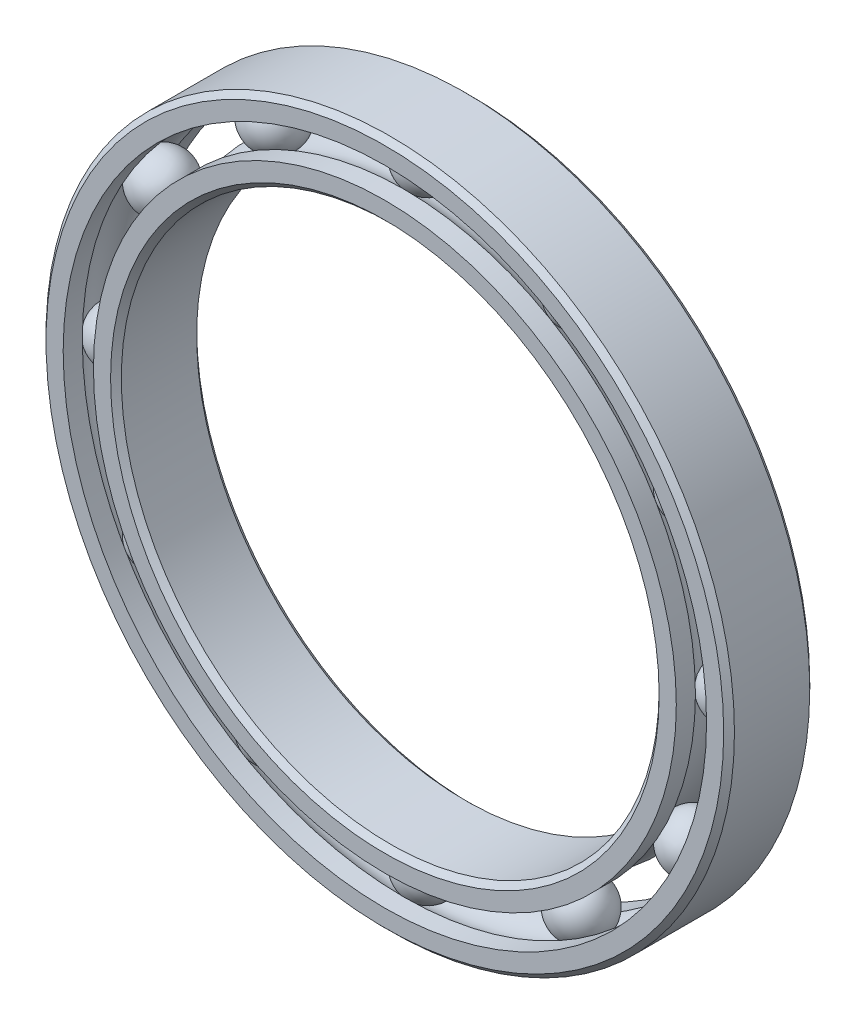
SolidWorks part; units mm, degrees
ref_plane "Front Plane" through (0, 0, 0) normal (0, 0, 1) x (1, 0, 0)
ref_plane "Top Plane" through (0, 0, 0) normal (0, 1, 0) x (1, 0, 0)
ref_plane "Right Plane" through (0, 0, 0) normal (1, 0, 0) x (0, 0, -1)
sketch "Sketch1" plane through (0, 0, 0) normal (1, 0, 0) x (0, 0, -1)
  line L0 (-2, 0) -> (2, 0) construction
  line L1 (0, 16) -> (0, -16) construction
  line L2 (1.75, 16) -> (-1.75, 16)
  line L3 (-1.75, 16) -> (-2, 15.75)
  line L4 (-2, 15.75) -> (-2, 14.9533)
  line L5 (-2, 14.9533) -> (-1.1111, 14.9533)
  line L6 (2, 14.9533) -> (1.1111, 14.9533)
  line L7 (2, 15.75) -> (2, 14.9533)
  line L8 (1.75, 16) -> (2, 15.75)
  line L9 (0, 16) -> (0, 14.25) construction
  line L10 (0, 14.25) -> (0, 12.5) construction
  arc A0 (-1.1111, 14.9533) -> (1.1111, 14.9533) centre (0, 14.25) cw
  point P14 (0, 12.5)
  dimension "Width" = 4
  dimension "OD" = 32
  dimension "D1" = 45
  dimension "D2" = 0.25
  dimension "Shaft Dia" = 25
  dimension "D3" = 2.2222
  dimension "D4" = 0.7033
revolve "Revolve1" add sketch "Sketch1" angle 360 about L0
sketch "Sketch3" plane through (0, 0, 0) normal (1, 0, 0) x (0, 0, -1)
  line L0 (-2, 13.5467) -> (-1.1111, 13.5467)
  line L1 (0, 16) -> (0, -16) construction
  line L2 (-2, 15.75) -> (-2, 14.9533) construction
  line L3 (-2, 13.5467) -> (-2, 12.75)
  line L4 (-1.75, 16) -> (-2, 15.75) construction
  line L5 (-2, 12.75) -> (-1.75, 12.5)
  line L6 (-1.75, 12.5) -> (1.75, 12.5)
  line L7 (1.75, 16) -> (1.75, -16) construction
  line L8 (1.75, 12.5) -> (2, 12.75)
  line L9 (2, -15.75) -> (2, 15.75) construction
  line L10 (2, 12.75) -> (2, 13.5467)
  line L11 (2, 13.5467) -> (1.1111, 13.5467)
  line L13 (1.75, 16) -> (2, 15.75) construction
  arc A0 (1.1111, 14.9533) -> (-1.1111, 14.9533) centre (0, 14.25) ccw construction
  arc A1 (1.1111, 13.5467) -> (-1.1111, 13.5467) centre (0, 14.25) cw
revolve "Revolve3" add sketch "Sketch3" angle 360 about L0
sketch "Sketch4" plane through (0, 0, 0) normal (1, 0, 0) x (0, 0, -1)
  line L0 (-1.315, 14.25) -> (1.315, 14.25)
  arc A2 (-1.315, 14.25) -> (1.315, 14.25) centre (0, 14.25) cw
  arc A3 (1.1111, 14.9533) -> (-1.1111, 14.9533) centre (0, 14.25) ccw construction
revolve "Revolve4" add sketch "Sketch4" angle 360 about L0
ref_axis "Axis1" through (0, 0, -2) along (0, 0, 1)
pattern_circular "CirPattern1" count 12 every 30 about axis through (0, 0, -2) along (0, 0, 1) of bodies 104
sketch "Sketch5" plane through (0, 0, 0) normal (1, 0, 0) x (0, 0, -1)
  line L0 (-2, 14.9533) -> (-1.1111, 14.9533) construction
  line L1 (-1.875, 14.9533) -> (-1.315, 14.9533)
  line L2 (-1.875, 14.9533) -> (-1.875, 13.5467)
  line L3 (-1.875, 13.5467) -> (-1.315, 13.5467)
  line L4 (-1.315, 14.9533) -> (-1.315, 13.5467)
  line L5 (-2, 13.5467) -> (-1.1111, 13.5467) construction
  line L6 (2, 14.9533) -> (1.1111, 14.9533) construction
  line L7 (1.875, 14.9533) -> (1.315, 14.9533)
  line L8 (1.875, 14.9533) -> (1.875, 13.5467)
  line L9 (1.875, 13.5467) -> (1.315, 13.5467)
  line L10 (1.315, 14.9533) -> (1.315, 13.5467)
  line L11 (2, 13.5467) -> (1.1111, 13.5467) construction
  line L12 (-1.75, 16) -> (-2, 15.75) construction
  point P18 (-1.875, 15.875)
equation "\"D2@Sketch1\" = \"Width@Sketch1\"*.05"
equation "\"D3@Sketch1\" = \"Width@Sketch1\"/2.25"
equation "\"D4@Sketch1\" = (((\"OD@Sketch1\"-\"Width@Sketch1\")/2)/3.25)/3.5"
equation "\"D2@CirPattern1\" = 360/\"Balls@CirPattern1\""
